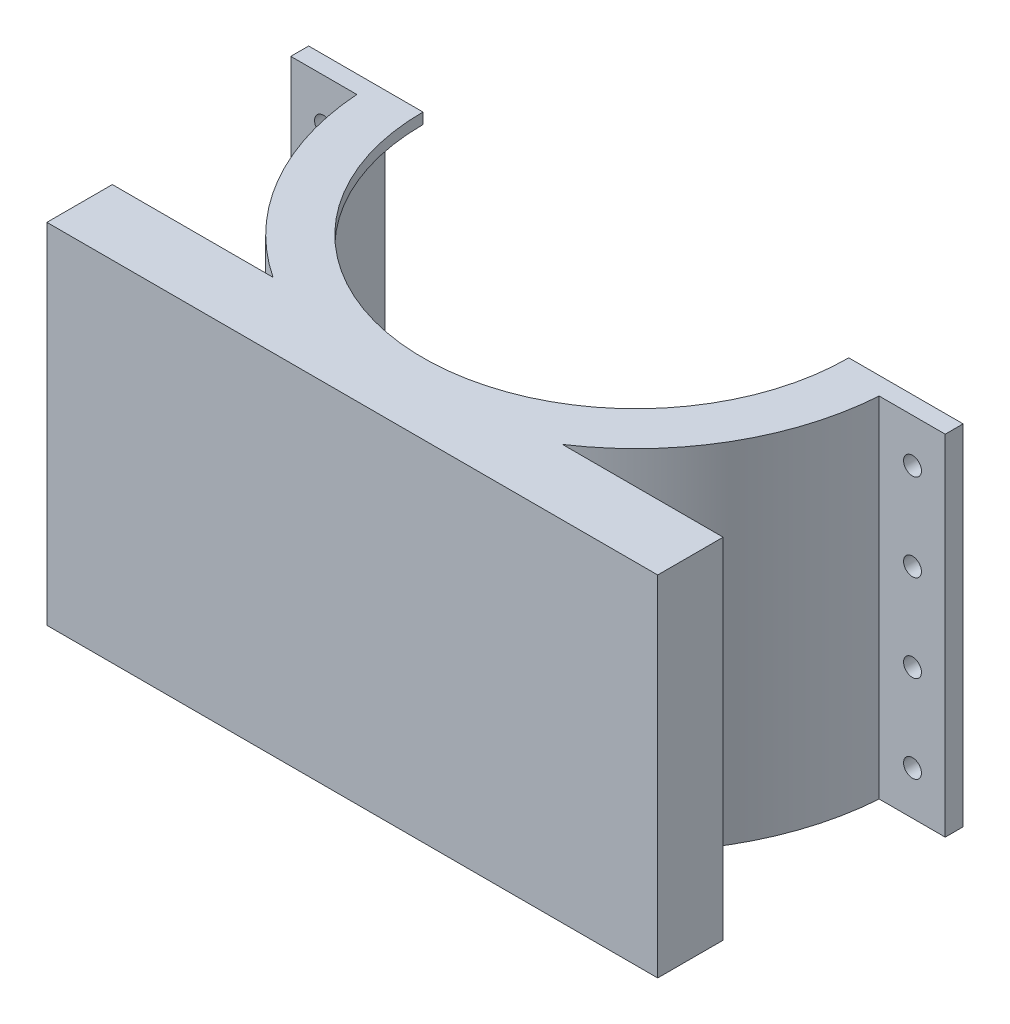
SolidWorks part; units mm, degrees
ref_plane "Front Plane" through (0, 0, 0) normal (0, 0, 1) x (1, 0, 0)
ref_plane "Top Plane" through (0, 0, 0) normal (0, 1, 0) x (1, 0, 0)
ref_plane "Right Plane" through (0, 0, 0) normal (1, 0, 0) x (0, 0, -1)
sketch "Sketch1" plane through (0, 0, 0) normal (0, 1, 0) x (1, 0, 0)
  line L0 (0, 7.77) -> (0, -6.8997) construction
  line L1 (-7.5, 0) -> (-1.5, 0)
  line L2 (-7.5, 0) -> (-7.5, -0.41)
  line L3 (-7.5, -0.41) -> (-5.986, -0.41)
  line L4 (7.5, 0) -> (7.5, -0.41)
  line L5 (-7, -5) -> (-3.3166, -5)
  line L6 (-7, -5) -> (-7, -6.5)
  line L7 (-7, -6.5) -> (7, -6.5)
  line L8 (7, -5) -> (7, -6.5)
  line L9 (-14.9199, 0) -> (13.6392, 0) construction
  line L10 (1.5, 0) -> (7.5, 0)
  line L11 (3.3166, -5) -> (7, -5)
  line L12 (5.986, -0.41) -> (7.5, -0.41)
  arc A0 (-4.88, 0) -> (4.88, 0) centre (0, 0) ccw
  arc A1 (-5.986, -0.41) -> (5.986, -0.41) centre (0, 0) ccw
  arc A2 (-1.5, 0) -> (1.5, 0) centre (0, 0) ccw
  arc A3 (-5.75, 0) -> (5.75, 0) centre (0, 0) ccw
  point P24 (0, -6.5)
  point P26 (-3.3166, -5)
  dimension "D3" = 1.5
  dimension "D4" = 6
  dimension "D5" = 4.88
  dimension "D6" = 0.25
  dimension "D1" = 15
  dimension "D2" = 0.41
  dimension "D7" = 5
  dimension "D8" = 1.5
  dimension "D10" = 14
  dimension "D11" = 1.514
  dimension "D12" = 1.514
extrude "Boss-Extrude2" add sketch "Sketch1" along normal mid plane 8 contours A2 L1 A0 L10 | A1 L5 L6 L7 L8 L11 | L1 A3 L10 A0 | A3 L1 L2 L3 A1 L12 L4 L10 region at (-6.625, 0, 0.1616) region at (-5.315, 0, 0.1286) region at (0, 0, 2.2208) region at (0, 0, 6.1408)
extrude "Cut-Extrude1" cut sketch "Sketch1<3>" against normal mid plane 7.5 contours A2 L1 A0 L10 | L1 A3 L10 A0 region at (-5.315, 0, 0.1286) region at (0, 0, 2.2208)
sketch "Sketch1<3>" plane through (0, 0, 0) normal (0, 1, 0) x (1, 0, 0) same geometry as "Sketch1"
extrude "Cut-Extrude2" cut sketch "Sketch1<4>" along normal blind 7.5 contours A2 L1 A0 L10 region at (0, 0, 2.2208)
sketch "Sketch1<4>" plane through (0, 0, 0) normal (0, 1, 0) x (1, 0, 0) same geometry as "Sketch1"
sketch "Sketch2" plane through (0, 0, 0.41) normal (0, 0, 1) x (1, 0, 0)
  line L0 (-10.5027, 0) -> (9.6924, 0) construction
  line L1 (0, 6.1509) -> (0, -5.2433) construction
  line L2 (-7.5, 4) -> (-7.5, -4) construction
  line L3 (-7, 4) -> (7, 4) construction
  circle A0 centre (-6.75, 3) radius 0.205
  circle A1 centre (-6.75, 1) radius 0.205
  circle A2 centre (-6.75, -1) radius 0.205
  circle A3 centre (-6.75, -3) radius 0.205
  circle A4 centre (6.75, -3) radius 0.205
  circle A5 centre (6.75, -1) radius 0.205
  circle A6 centre (6.75, 1) radius 0.205
  circle A7 centre (6.75, 3) radius 0.205
  dimension "D1" = 0.41
  dimension "D2" = 0.75
  dimension "D3" = 1
  dimension "D4" = 2
  dimension "D5" = 0.75
extrude "Cut-Extrude3" cut sketch "Sketch2" against normal blind 7.5
